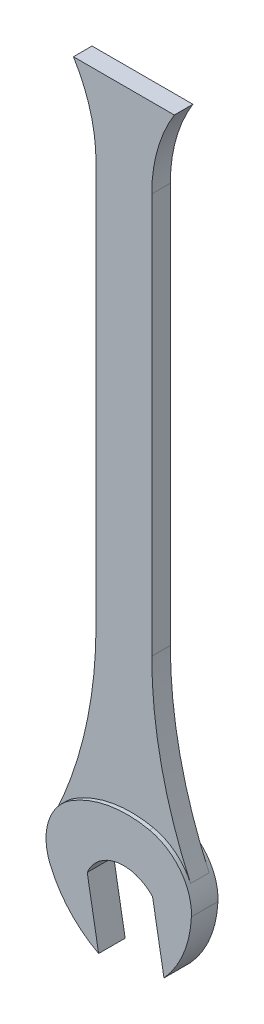
SolidWorks part; units mm, degrees
ref_plane "Front Plane" through (0, 0, 0) normal (1, 0, 0) x (0, 1, 0)
ref_plane "Top Plane" through (0, 0, 0) normal (0, 0, 1) x (0, 1, 0)
ref_plane "Right Plane" through (0, 0, 0) normal (0, 1, 0) x (-1, 0, 0)
sketch "Sketch2" plane through (0, 0, 0) normal (0, 0, 1) x (0, 1, 0)
  line L0 (-1.3783, 7.8169) -> (-16.8371, 5.0911)
  line L1 (1.3783, -7.8169) -> (-14.0804, -10.5427)
  line L2 (-1.3783, 7.8169) -> (1.3783, -7.8169) construction
  line L3 (-5.0941, -0.8982) -> (0, 0) construction
  line L4 (-5.0941, -0.8982) -> (-10.0056, -1.7643) construction
  line L5 (0, 0) -> (-15.9394, 0) construction
  line L6 (-14.0804, -10.5427) -> (-16.8371, 5.0911) construction
  line L7 (-4.1052, 16.7007) -> (1.8543, -17.0976) construction
  line L8 (14.8371, -7.0558) -> (11.5291, 11.7048) construction
  line L9 (-14.3514, 15.2013) -> (9.6201, 19.4282) construction
  line L10 (-9.4772, -19.403) -> (13.9076, -15.2796) construction
  line L11 (49.692, 6.6675) -> (145.8984, 6.6675)
  line L12 (164.9484, 12.065) -> (164.9484, -12.065)
  line L13 (0, 0) -> (164.9484, 0) construction
  line L14 (145.8984, -6.6675) -> (50.1453, -6.6675)
  arc A0 (-1.3783, 7.8169) -> (1.3783, -7.8169) centre (-5.0941, -0.8982) cw
  arc A1 (-16.8371, 5.0911) -> (-4.1052, 16.7007) centre (5.6286, -6.7602) cw
  arc A2 (-4.1052, 16.7007) -> (11.5291, 11.7048) centre (0.7617, 4.9703) cw
  arc A3 (11.5291, 11.7048) -> (14.8371, -7.0558) centre (-10.0056, -1.7643) cw
  arc A4 (14.8371, -7.0558) -> (1.8543, -17.0976) centre (2.4157, -4.41) cw
  arc A5 (1.8543, -17.0976) -> (-14.0804, -10.5427) centre (2.9771, 8.2776) cw
  arc A6 (6.1984, 16.4477) -> (49.692, 6.6675) centre (49.692, 108.2675) ccw
  arc A7 (145.8984, 6.6675) -> (164.9484, 12.065) centre (145.8984, 42.9839) ccw
  arc A8 (145.8984, -6.6675) -> (164.9484, -12.065) centre (145.8984, -42.9839) cw
  arc A9 (50.1453, -6.6675) -> (7.719, -15.9497) centre (50.1453, -108.2675) ccw
  dimension "D2" = 9.4742
  dimension "D3" = 25.4
  dimension "D4" = 12.7
  dimension "D5" = 25.4
  dimension "D7" = 10
  dimension "D9" = 34.925
  dimension "D11" = 101.6
  dimension "D1" = 15.875
  dimension "D6" = 10.16
  dimension "D8" = 15.6972
  dimension "D10" = 158.75
  dimension "D12" = 19.05
  dimension "D13" = 24.13
  dimension "D14" = 6.6675
extrude "Boss-Extrude1" add sketch "Sketch2" along normal blind 3.175 and the other way blind 3.175 contours A5 A4 A3 A2 A1 L0 A0 L1 region at (-6.921, -9.19, 0)
extrude "Boss-Extrude2" add sketch "Sketch2<3>" along normal blind 2.2225 and the other way blind 2.2225 contours A9 L14 A8 L12 A7 L11 A6 A2 A3 A4 region at (-0.0373, 86.7619, 0)
sketch "Sketch2<3>" plane through (0, 0, 0) normal (0, 0, 1) x (0, 1, 0) same geometry as "Sketch2"
